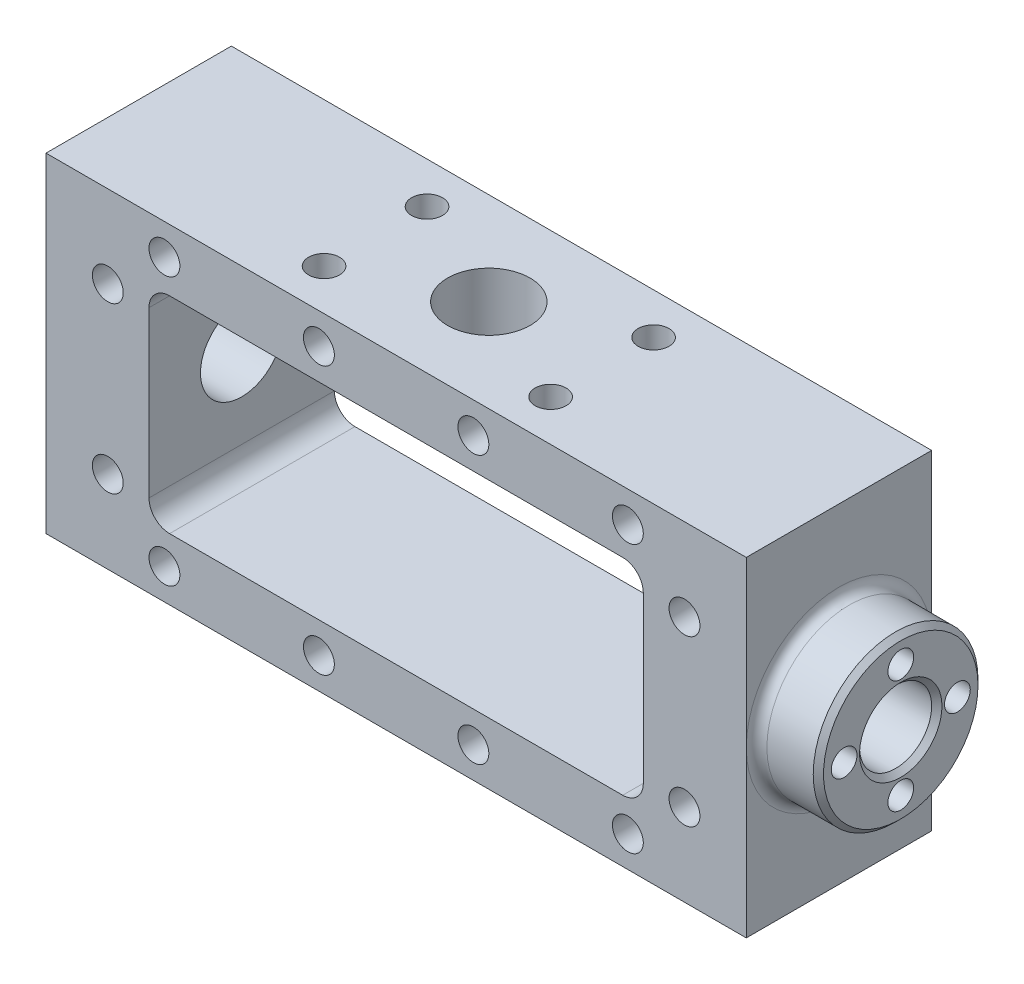
SolidWorks part; units mm, degrees
ref_plane "Front Plane" through (0, 0, 0) normal (0, 0, 1) x (1, 0, 0)
ref_plane "Top Plane" through (0, 0, 0) normal (0, 1, 0) x (1, 0, 0)
ref_plane "Right Plane" through (0, 0, 0) normal (1, 0, 0) x (0, 0, -1)
sketch "Sketch2" plane through (0, 0, 0) normal (0, 0, 1) x (1, 0, 0)
  line L1 (34, -16) -> (-34, -16)
  line L2 (34, -16) -> (34, 16)
  line L3 (34, 16) -> (-34, 16)
  line L4 (-34, -16) -> (-34, 16)
  line L5 (34, -16) -> (-34, 16) construction
  line L6 (34, 16) -> (-34, -16) construction
  point P0 (0, 0)
  dimension "D1" = 16
  dimension "D2" = 68
extrude "Boss-Extrude1" add sketch "Sketch2" along normal blind 18
sketch "Sketch3" plane through (34, 0, 0) normal (1, 0, 0) x (0, 0, -1)
  line L0 (-18, -16) -> (0, -16) construction
  circle A0 centre (-9, 0) radius 8
  point P5 (-9, -16)
  dimension "D1" = 16
extrude "Boss-Extrude2" add sketch "Sketch3" along normal blind 6
fillet "Fillet1" radius 1 1 edges at (34, 0, 1)
sketch "Sketch4" plane through (-34, 0, 0) normal (-1, 0, 0) x (0, 0, 1)
  line L0 (9, 16) -> (9, 0) construction
  line L1 (18, 16) -> (0, 16) construction
  line L2 (9, 0) -> (0, 0) construction
  circle A0 centre (9, 0) radius 4
  dimension "D1" = 8
extrude "Cut-Extrude1" cut sketch "Sketch4" against normal blind 10
sketch "Sketch5" plane through (0, 0, 18) normal (0, 0, 1) x (1, 0, 0)
  line L1 (22, -10) -> (-22, -10)
  line L2 (24, -8) -> (24, 8)
  line L3 (22, 10) -> (-22, 10)
  line L4 (-24, -8) -> (-24, 8)
  line L5 (24, -10) -> (-24, 10) construction
  line L6 (24, 10) -> (-24, -10) construction
  arc A0 (-22, 10) -> (-24, 8) centre (-22, 8) ccw
  arc A1 (24, 8) -> (22, 10) centre (22, 8) ccw
  arc A2 (22, -10) -> (24, -8) centre (22, -8) ccw
  arc A3 (-22, -10) -> (-24, -8) centre (-22, -8) cw
  point P0 (0, 0)
  dimension "D3" = 2
  dimension "D1" = 48
  dimension "D2" = 10
extrude "Cut-Extrude2" cut sketch "Sketch5" against normal through all
sketch "Sketch6" plane through (0, 0, 18) normal (0, 0, 1) x (1, 0, 0)
  line L0 (34, 16) -> (-34, 16) construction
  line L1 (-34, 16) -> (-34, -16) construction
  line L2 (34, 0) -> (34, 16) construction
  line L3 (-34, 0) -> (0, 0) construction
  line L4 (0, 0) -> (0, -16) construction
  line L5 (-34, -16) -> (34, -16) construction
  line L6 (40, -8) -> (40, 8) construction
  line L7 (35, -8) -> (40, -8) construction
  circle A0 centre (-22.5, 13) radius 1.5
  circle A1 centre (-7.5, 13) radius 1.5
  circle A2 centre (7.5, 13) radius 1.5
  circle A3 centre (22.5, 13) radius 1.5
  circle A5 centre (22.5, -13) radius 1.5
  circle A6 centre (7.5, -13) radius 1.5
  circle A7 centre (-7.5, -13) radius 1.5
  circle A8 centre (-22.5, -13) radius 1.5
  circle A9 centre (28, -8) radius 1.5
  circle A10 centre (28, 8) radius 1.5
  circle A11 centre (-28, 8) radius 1.5
  circle A12 centre (-28, -8) radius 1.5
  dimension "D2" = 3
  dimension "D7" = 3
  dimension "D1" = 3
  dimension "D3" = 11.5
  dimension "D4" = 11.5
  dimension "D5" = 7.5
  dimension "D6" = 7.5
  dimension "D8" = 12
extrude "Cut-Extrude3" cut sketch "Sketch6" against normal through all
sketch "Sketch7" plane through (40, 0, 0) normal (1, 0, 0) x (0, 0, -1)
  circle A0 centre (-9, 0) radius 3.5
  dimension "D1" = 7
extrude "Cut-Extrude4" cut sketch "Sketch7" against normal blind 12
sketch "Sketch8" plane through (28, 0, 0) normal (1, 0, 0) x (0, 0, -1)
  circle A0 centre (-9, 0) radius 3
  dimension "D1" = 6
extrude "Cut-Extrude5" cut sketch "Sketch8" against normal through all
sketch "Sketch9" plane through (40, 0, 0) normal (1, 0, 0) x (0, 0, -1)
  circle A0 centre (-9, 5.5) radius 1.25
  circle A1 centre (-9, 0) radius 5.5 construction
  circle A2 centre (-9, -5.5) radius 1.25
  circle A3 centre (-3.5, 0) radius 1.25
  circle A4 centre (-14.5, 0) radius 1.25
  dimension "D1" = 11
  dimension "D2" = 2.5
  dimension "D3" = 2.5
  dimension "D4" = 2.5
  dimension "D5" = 2.5
extrude "Cut-Extrude6" cut sketch "Sketch9" against normal blind 5
sketch "Sketch10" plane through (0, 0, 0) normal (0, 1, 0) x (1, 0, 0)
  line L0 (-34, -18) -> (-34, 0) construction
  line L1 (0, 0) -> (0, -9) construction
  line L2 (0, -9) -> (-34, -9) construction
  circle A0 centre (0, -9) radius 4
  circle A1 centre (-11, -4) radius 1.5
  circle A2 centre (11, -4) radius 1.5
  circle A3 centre (11, -14) radius 1.5
  circle A4 centre (-11, -14) radius 1.5
  point P5 (-34, -9)
  dimension "D1" = 8
  dimension "D2" = 3
  dimension "D3" = 5
  dimension "D4" = 11
extrude "Cut-Extrude9" cut sketch "Sketch10" along normal through all
chamfer "Chamfer1" distance 0.5 angle 45 1 edges at (-34, 0, 13)
chamfer "Chamfer2" distance 0.5 angle 45 2 edges at (40, 0, 1) (40, 0, 5.5)
